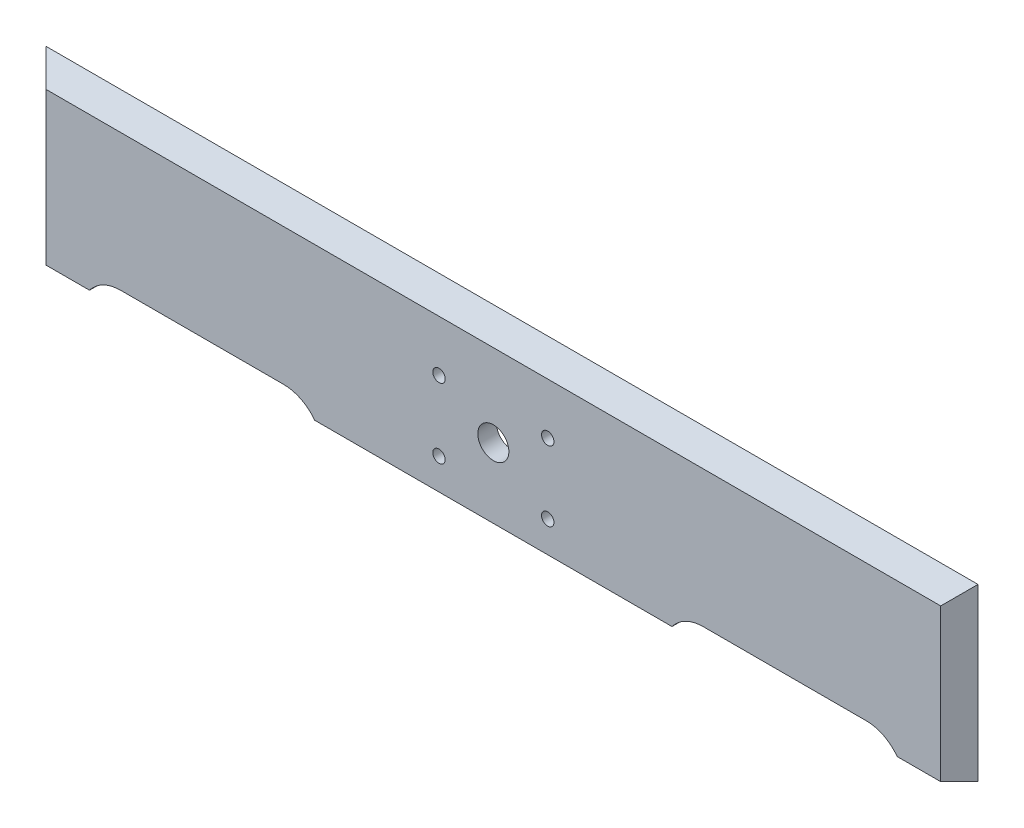
SolidWorks part; units mm, degrees
material "Teak"
ref_plane "Front Plane" through (0, 0, 0) normal (0, 0, 1) x (1, 0, 0)
ref_plane "Top Plane" through (0, 0, 0) normal (0, 1, 0) x (1, 0, 0)
ref_plane "Right Plane" through (0, 0, 0) normal (1, 0, 0) x (0, 0, -1)
sketch "Sketch1" plane through (0, 0, 0) normal (0, 0, 1) x (1, 0, 0)
  line L0 (0, 0) -> (0, -10)
  line L1 (60, 0) -> (165, 0)
  line L2 (0, 0) -> (0, 100)
  line L3 (0, 100) -> (600, 100)
  line L4 (600, 0) -> (600, 100)
  line L5 (0, -10) -> (40, -10)
  line L6 (600, 0) -> (600, -10)
  line L7 (600, -10) -> (560, -10)
  line L8 (300, 100) -> (300, -10) construction
  line L9 (185, -10) -> (415, -10)
  line L10 (435, 0) -> (540, 0)
  arc A0 (40, -10) -> (60, 0) centre (60, -25) cw
  arc A1 (560, -10) -> (540, 0) centre (540, -25) ccw
  arc A2 (185, -10) -> (165, 0) centre (165, -25) ccw
  arc A3 (415, -10) -> (435, 0) centre (435, -25) cw
  dimension "D7" = 25
  dimension "D8" = 25
  dimension "D13" = 25
  dimension "D14" = 25
  dimension "D1" = 600
  dimension "D2" = 100
  dimension "D3" = 10
  dimension "D4" = 10
  dimension "D5" = 40
  dimension "D6" = 40
  dimension "D9" = 10
  dimension "D10" = 10
  dimension "D11" = 115
  dimension "D12" = 115
extrude "Boss-Extrude1" add sketch "Sketch1" along normal blind 12
chamfer "Chamfer1" distance 12 angle 45 3 edges at (300, 100, 12) (600, 45, 12) (0, 45, 12)
sketch "Sketch2" plane through (0, 0, 0) normal (0, 0, -1) x (-1, 0, 0)
  line L0 (-600, 100) -> (0, 100) construction
  line L1 (-375, 80) -> (-225, 80)
  line L2 (-375, 80) -> (-375, -10)
  line L3 (-375, -10) -> (-225, -10)
  line L4 (-225, 80) -> (-225, -10)
  line L7 (-185, -10) -> (-415, -10) construction
  circle A0 centre (-335, 55) radius 4
  circle A1 centre (-265, 55) radius 4
  circle A2 centre (-300, 35) radius 10
  circle A3 centre (-335, 10) radius 4
  circle A4 centre (-265, 10) radius 4
  point P12 (-300, 100)
  point P13 (-300, 80)
  point P17 (-225, 35)
  point P21 (0, 0)
  point P22 (0, 0)
  point P23 (0, 0)
  dimension "D1" = 8
  dimension "D2" = 8
  dimension "D8" = 20
  dimension "D7" = 8
  dimension "D10" = 8
  dimension "D3" = 150
  dimension "D4" = 40
  dimension "D5" = 40
  dimension "D6" = 25
  dimension "D9" = 20
  dimension "D11" = 20
extrude "Cut-Extrude1" cut sketch "Sketch2" against normal through all contours A0 | A2 | A1 | A3 | A4 region at (335, 55, 0) region at (265, 55, 0) region at (300, 35, 0)
